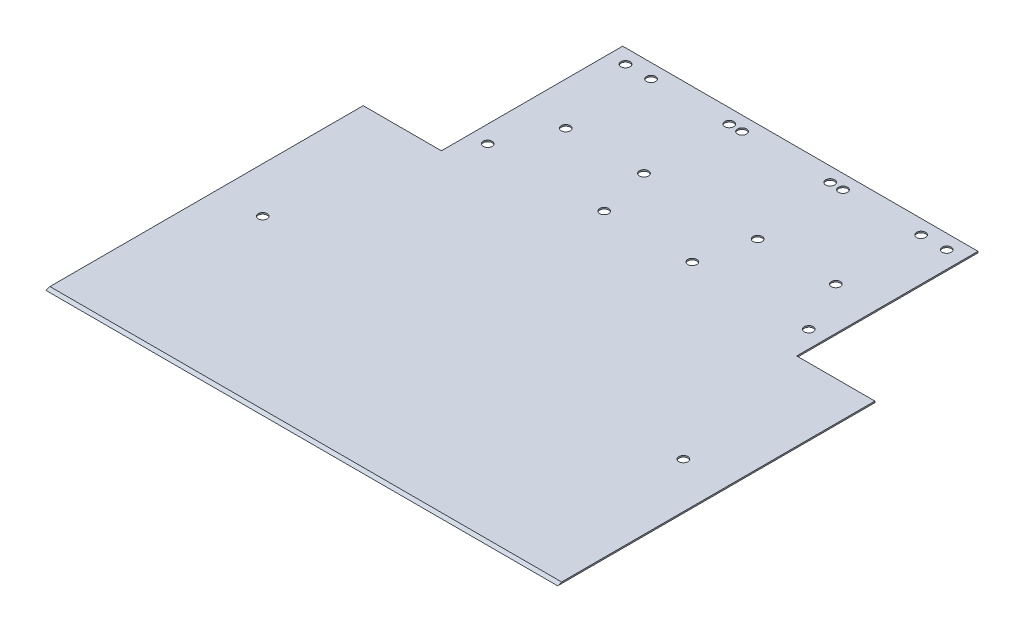
SolidWorks part; units mm, degrees
ref_plane "Alzado" through (0, 0, 0) normal (0, 0, 1) x (1, 0, 0)
ref_plane "Planta" through (0, 0, 0) normal (0, 1, 0) x (1, 0, 0)
ref_plane "Vista lateral" through (0, 0, 0) normal (1, 0, 0) x (0, 0, -1)
sketch "Croquis2" plane through (0, 0, 0) normal (0, 1, 0) x (1, 0, 0)
  line L0 (-90, 25.54) -> (-62.5, 25.54)
  line L1 (90, -86.05) -> (-90, -86.05)
  line L2 (90, -86.05) -> (90, 25.54)
  line L3 (62.5, 89.31) -> (-62.5, 89.31)
  line L4 (-90, -86.05) -> (-90, 25.54)
  line L5 (90, -86.05) -> (-62.5, 59.7569) construction
  line L6 (62.5, 59.7569) -> (-90, -86.05) construction
  line L7 (-62.5, 25.54) -> (-62.5, 89.31)
  line L8 (0, 3.26) -> (0, 89.31) construction
  line L9 (90, 25.54) -> (62.5, 25.54)
  line L10 (62.5, 25.54) -> (62.5, 89.31)
  point P0 (0, 0)
  dimension "D1" = 125
  dimension "D2" = 180
  dimension "D3" = 111.59
  dimension "D4" = 63.77
extrude "Saliente-Extruir1" add sketch "Croquis2" along normal blind 0.5
sketch "Croquis3" plane through (90, 0, 0) normal (1, 0, 0) x (0, 0, -1)
  line L0 (-86.05, 0) -> (-84.6763, 0.5)
  line L1 (-86.05, 0.5) -> (25.54, 0.5) construction
  line L2 (-84.6763, 0.5) -> (-86.05, 0.5)
  line L3 (-86.05, 0.5) -> (-86.05, 0)
  dimension "D1" = 70
sketch "Croquis5" plane through (0, 0.5, 0) normal (0, 1, 0) x (1, 0, 0)
  circle A0 centre (74, -25.8204) radius 1.585
sketch "Croquis6" plane through (0, 0.5, 0) normal (0, 1, 0) x (1, 0, 0)
  circle A0 centre (-56.5, 35.81) radius 1.585
  circle A1 centre (-15.5, 35.81) radius 1.585
  circle A2 centre (-15.5, 84.31) radius 1.585
  circle A3 centre (-56.5, 84.31) radius 1.585
extrude "Cortar-Extruir4" cut sketch "Croquis6" against normal up to next
sketch "Croquis7" plane through (0, 0.5, 0) normal (0, 1, 0) x (1, 0, 0)
  circle A0 centre (56.5, 35.81) radius 1.585
  circle A1 centre (15.5, 35.81) radius 1.585
  circle A2 centre (15.5, 84.31) radius 1.585
  circle A3 centre (56.5, 84.31) radius 1.585
extrude "Cortar-Extruir5" cut sketch "Croquis7" against normal up to next
mirror "Simetría3" about plane through (0, 0, 0) normal (1, 0, 0) of "Saliente-Extruir1"
sketch "Croquis8" plane through (0, 0.5, 0) normal (0, 1, 0) x (1, 0, 0)
  circle A0 centre (-20, 54.31) radius 1.585
  circle A1 centre (-47.5, 54.31) radius 1.585
  circle A2 centre (-47.5, 84.31) radius 1.585
  circle A3 centre (-20, 84.31) radius 1.585
extrude "Cortar-Extruir6" cut sketch "Croquis8" against normal up to next
mirror "Simetría4" about plane through (0, 0, 0) normal (1, 0, 0) of "Cortar-Extruir6"
sketch "Croquis9" plane through (0, 0, 0) normal (0, -1, 0) x (1, 0, 0)
  circle A0 centre (56.5, -35.81) radius 1.585
  circle A2 centre (15.5, -35.81) radius 1.585
  circle A3 centre (15.5, -84.31) radius 1.585
  circle A4 centre (56.5, -84.31) radius 1.585
extrude "Cortar-Extruir7" cut sketch "Croquis9" against normal up to next
mirror "Simetría5" about plane through (0, 0, 0) normal (1, 0, 0) of "Cortar-Extruir7"
extrude "Cortar-Extruir8" cut sketch "Croquis5" against normal up to next
mirror "Simetría6" about plane through (0, 0, 0) normal (1, 0, 0) of "Cortar-Extruir8"
extrude "Cortar-Extruir9" cut sketch "Croquis3" against normal up to next
